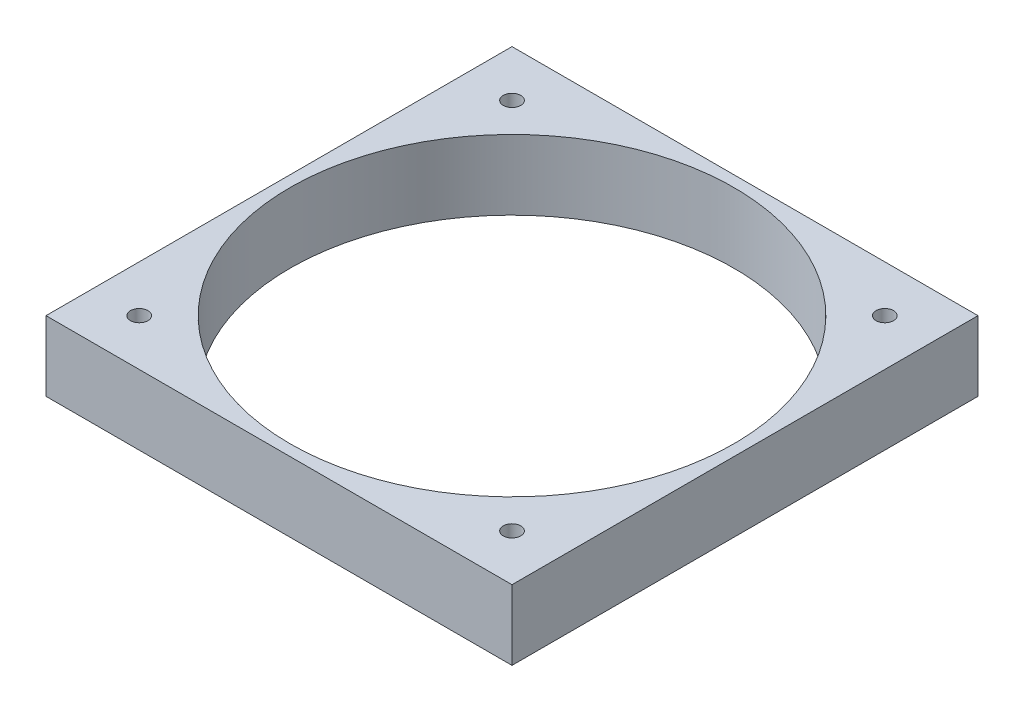
SolidWorks part; units mm, degrees
ref_plane "Front Plane" through (0, 0, 0) normal (0, 0, 1) x (1, 0, 0)
ref_plane "Top Plane" through (0, 0, 0) normal (0, 1, 0) x (1, 0, 0)
ref_plane "Right Plane" through (0, 0, 0) normal (1, 0, 0) x (0, 0, -1)
sketch "Sketch1" plane through (0, 0, 0) normal (0, 1, 0) x (1, 0, 0)
  line L0 (0, 40) -> (40, 0) construction
  line L1 (0, 0) -> (40, 0)
  line L2 (0, 0) -> (0, 40)
  line L3 (0, 40) -> (40, 40)
  line L4 (40, 0) -> (40, 40)
  line L6 (36, 36) -> (4, 36) construction
  line L7 (36, 36) -> (36, 4) construction
  line L8 (36, 4) -> (4, 4) construction
  line L9 (4, 36) -> (4, 4) construction
  line L10 (36, 36) -> (4, 4) construction
  line L11 (36, 4) -> (4, 36) construction
  circle A0 centre (4, 36) radius 0.75
  circle A1 centre (36, 36) radius 0.75
  circle A2 centre (4, 4) radius 0.75
  circle A3 centre (36, 4) radius 0.75
  circle A4 centre (20, 20) radius 19.05
  point P5 (20, 20)
  dimension "D4" = 38.1
  dimension "D5" = 1.5
  dimension "D1" = 40
  dimension "D2" = 40
  dimension "D3" = 32
extrude "Boss-Extrude1" add sketch "Sketch1" along normal blind 6
ref_plane "Plane1" through (20, 0, 0) normal (1, 0, 0) x (0, 0, -1)
ref_plane "Plane2" through (0, 0, -20) normal (0, 0, -1) x (-1, 0, 0)
equation "\"D2@Sketch1\"=\"D1@Sketch1\""
